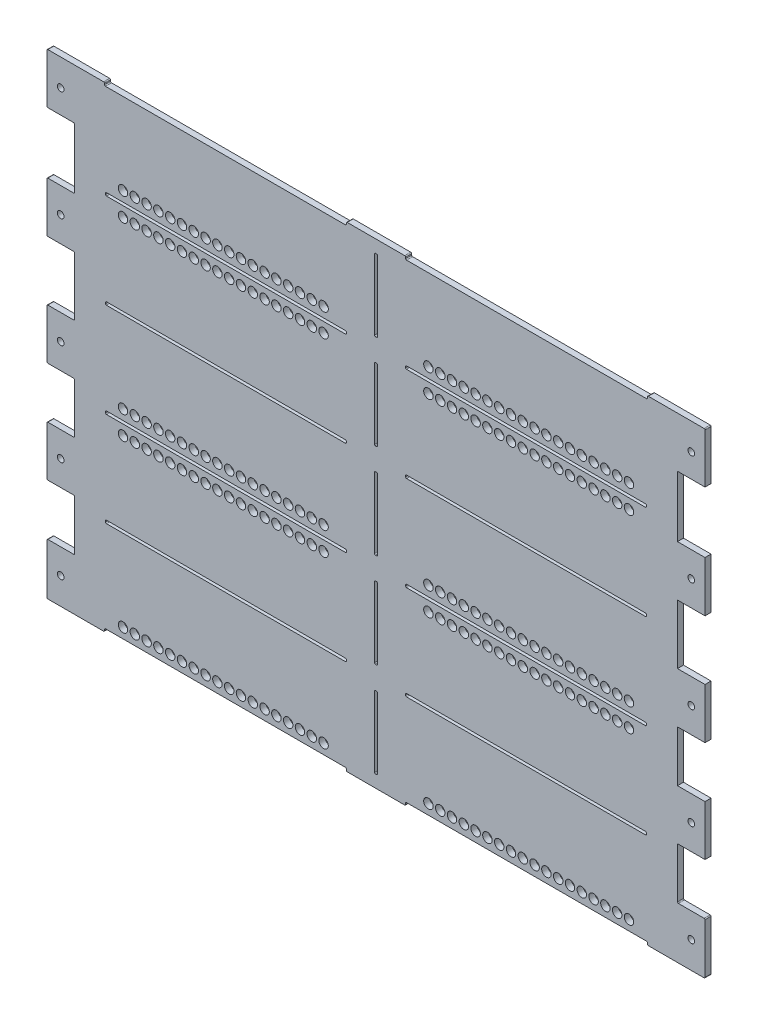
SolidWorks part; units mm, degrees
material "6061-T6 (SS)"
ref_plane "X-Y Datum" through (0, 0, 0) normal (0, 0, 1) x (1, 0, 0)
ref_plane "X-Z Datum" through (0, 0, 0) normal (0, 1, 0) x (1, 0, 0)
ref_plane "Y-Z Datum" through (0, 0, 0) normal (1, 0, 0) x (0, 0, -1)
sketch "Sketch1" plane through (0, 0, 0) normal (0, 0, 1) x (1, 0, 0)
  line L0 (-1.27, -1.27) -> (-1.27, 95.3084)
  line L1 (0, 0) -> (310.8274, 0)
  line L2 (0, 0) -> (0, 94.0384)
  line L3 (0, 94.0384) -> (310.8274, 94.0384)
  line L4 (310.8274, 0) -> (310.8274, 94.0384)
  line L5 (-1.27, 95.3084) -> (312.0974, 95.3084)
  line L6 (312.0974, -1.27) -> (312.0974, 95.3084)
  line L7 (-1.27, -1.27) -> (312.0974, -1.27)
  line L8 (-2.8575, 96.8959) -> (313.6849, 96.8959)
  line L9 (313.6849, -2.8575) -> (313.6849, 96.8959)
  line L10 (-2.8575, -2.8575) -> (313.6849, -2.8575)
  line L11 (-2.8575, -2.8575) -> (-2.8575, 96.8959)
  line L12 (0, 99.7534) -> (310.8274, 99.7534)
  line L13 (310.8274, 193.7918) -> (310.8274, 99.7534)
  line L14 (0, 193.7918) -> (310.8274, 193.7918)
  line L15 (0, 193.7918) -> (0, 99.7534)
  line L16 (-1.27, 195.0618) -> (312.0974, 195.0618)
  line L17 (312.0974, 195.0618) -> (312.0974, 98.4834)
  line L18 (-1.27, 98.4834) -> (312.0974, 98.4834)
  line L19 (-1.27, 195.0618) -> (-1.27, 98.4834)
  line L20 (-2.8575, 196.6493) -> (-2.8575, 96.8959)
  line L21 (-2.8575, 196.6493) -> (630.2273, 196.6493)
  line L23 (-2.8575, 296.4028) -> (630.2273, 296.4028)
  line L24 (-1.27, 198.2368) -> (-1.27, 294.8153)
  line L25 (-1.27, 294.8153) -> (312.0974, 294.8153)
  line L26 (312.0974, 198.2368) -> (312.0974, 294.8153)
  line L27 (-1.27, 198.2368) -> (312.0974, 198.2368)
  line L28 (0, 199.5068) -> (0, 293.5453)
  line L29 (0, 199.5068) -> (310.8274, 199.5068)
  line L30 (310.8274, 199.5068) -> (310.8274, 293.5453)
  line L31 (0, 293.5453) -> (310.8274, 293.5453)
  line L33 (313.6849, 96.8959) -> (313.6849, 196.6493)
  line L34 (-2.8575, 396.1562) -> (630.2273, 396.1562)
  line L35 (-1.27, 394.5687) -> (312.0974, 394.5687)
  line L36 (312.0974, 394.5687) -> (312.0974, 297.9903)
  line L37 (-1.27, 297.9903) -> (312.0974, 297.9903)
  line L38 (-1.27, 394.5687) -> (-1.27, 297.9903)
  line L39 (0, 393.2987) -> (310.8274, 393.2987)
  line L40 (310.8274, 393.2987) -> (310.8274, 299.2603)
  line L41 (0, 299.2603) -> (310.8274, 299.2603)
  line L42 (0, 393.2987) -> (0, 299.2603)
  line L43 (-2.8575, 296.4028) -> (-2.8575, 196.6493)
  line L44 (-2.8575, 495.9096) -> (-2.8575, 296.4028)
  line L45 (313.6849, 495.9096) -> (313.6849, 296.4028)
  line L46 (313.6849, 196.6493) -> (313.6849, 296.4028)
  line L47 (-2.8575, 495.9096) -> (630.2273, 495.9096)
  line L48 (-1.27, 397.7437) -> (-1.27, 494.3221)
  line L49 (-1.27, 494.3221) -> (312.0974, 494.3221)
  line L50 (312.0974, 397.7437) -> (312.0974, 494.3221)
  line L51 (-1.27, 397.7437) -> (312.0974, 397.7437)
  line L52 (0, 399.0137) -> (0, 493.0521)
  line L53 (0, 493.0521) -> (310.8274, 493.0521)
  line L54 (310.8274, 399.0137) -> (310.8274, 493.0521)
  line L55 (0, 399.0137) -> (310.8274, 399.0137)
  line L56 (313.6849, 595.663) -> (313.6849, 495.9096) construction
  line L57 (628.6398, 397.7437) -> (315.2724, 397.7437)
  line L58 (315.2724, 397.7437) -> (315.2724, 494.3221)
  line L59 (628.6398, 494.3221) -> (315.2724, 494.3221)
  line L60 (628.6398, 397.7437) -> (628.6398, 494.3221)
  line L61 (627.3698, 399.0137) -> (316.5424, 399.0137)
  line L62 (316.5424, 399.0137) -> (316.5424, 493.0521)
  line L63 (627.3698, 493.0521) -> (316.5424, 493.0521)
  line L64 (627.3698, 399.0137) -> (627.3698, 493.0521)
  line L65 (630.2273, 495.9096) -> (630.2273, 296.4028)
  line L66 (628.6398, 394.5687) -> (628.6398, 297.9903)
  line L67 (628.6398, 297.9903) -> (315.2724, 297.9903)
  line L68 (315.2724, 394.5687) -> (315.2724, 297.9903)
  line L69 (628.6398, 394.5687) -> (315.2724, 394.5687)
  line L70 (627.3698, 393.2987) -> (627.3698, 299.2603)
  line L71 (627.3698, 299.2603) -> (316.5424, 299.2603)
  line L72 (316.5424, 393.2987) -> (316.5424, 299.2603)
  line L73 (627.3698, 393.2987) -> (316.5424, 393.2987)
  line L74 (630.2273, 296.4028) -> (630.2273, 196.6493)
  line L75 (628.6398, 198.2368) -> (315.2724, 198.2368)
  line L76 (315.2724, 198.2368) -> (315.2724, 294.8153)
  line L77 (628.6398, 294.8153) -> (315.2724, 294.8153)
  line L78 (628.6398, 198.2368) -> (628.6398, 294.8153)
  line L79 (627.3698, 199.5068) -> (316.5424, 199.5068)
  line L80 (316.5424, 199.5068) -> (316.5424, 293.5453)
  line L81 (627.3698, 293.5453) -> (316.5424, 293.5453)
  line L82 (627.3698, 199.5068) -> (627.3698, 293.5453)
  line L83 (630.2273, 196.6493) -> (630.2273, 96.8959)
  line L84 (628.6398, 195.0618) -> (628.6398, 98.4834)
  line L85 (628.6398, 98.4834) -> (315.2724, 98.4834)
  line L86 (315.2724, 195.0618) -> (315.2724, 98.4834)
  line L87 (628.6398, 195.0618) -> (315.2724, 195.0618)
  line L88 (627.3698, 193.7918) -> (627.3698, 99.7534)
  line L89 (627.3698, 193.7918) -> (316.5424, 193.7918)
  line L90 (316.5424, 193.7918) -> (316.5424, 99.7534)
  line L91 (627.3698, 99.7534) -> (316.5424, 99.7534)
  line L92 (630.2273, -2.8575) -> (630.2273, 96.8959)
  line L93 (630.2273, -2.8575) -> (313.6849, -2.8575)
  line L94 (313.6849, -2.8575) -> (313.6849, 96.8959)
  line L95 (630.2273, 96.8959) -> (313.6849, 96.8959)
  line L96 (628.6398, -1.27) -> (315.2724, -1.27)
  line L97 (315.2724, -1.27) -> (315.2724, 95.3084)
  line L98 (628.6398, 95.3084) -> (315.2724, 95.3084)
  line L99 (628.6398, -1.27) -> (628.6398, 95.3084)
  line L100 (627.3698, 94.0384) -> (316.5424, 94.0384)
  line L101 (316.5424, 0) -> (316.5424, 94.0384)
  line L102 (627.3698, 0) -> (316.5424, 0)
  line L103 (627.3698, 0) -> (627.3698, 94.0384)
  point P56 (313.6849, 396.1562)
  dimension "D1" = 310.8274
  dimension "D2" = 94.0384
  dimension "D3" = 1.27
  dimension "D4" = 1.5875
sketch "Sketch2" plane through (0, 0, 0) normal (0, 0, 1) x (1, 0, 0)
  line L0 (0, 47.0192) -> (310.8274, 47.0192) construction
  line L1 (-1.27, -1.27) -> (628.6398, -1.27)
  line L2 (-1.27, -1.27) -> (-1.27, 494.3221)
  line L3 (-1.27, 494.3221) -> (628.6398, 494.3221)
  line L4 (628.6398, -1.27) -> (628.6398, 494.3221)
  line L5 (0, 0) -> (0, 94.0384) construction
  line L6 (310.8274, 0) -> (310.8274, 94.0384) construction
  line L7 (155.4137, 47.0192) -> (155.4137, 163.8162) construction
  line L8 (-2.8575, 96.8959) -> (313.6849, 96.8959) construction
  line L9 (28.4137, 95.3084) -> (282.4137, 95.3084)
  line L10 (28.4137, 95.3084) -> (28.4137, 98.4834)
  line L11 (28.4137, 98.4834) -> (282.4137, 98.4834)
  line L12 (282.4137, 95.3084) -> (282.4137, 98.4834)
  line L13 (28.4137, 95.3084) -> (282.4137, 98.4834) construction
  line L14 (28.4137, 98.4834) -> (282.4137, 95.3084) construction
  line L15 (-1.27, 98.4834) -> (312.0974, 98.4834) construction
  line L16 (-2.8575, 196.6493) -> (630.2273, 196.6493) construction
  line L17 (28.4137, 195.0618) -> (282.4137, 195.0618)
  line L18 (28.4137, 195.0618) -> (28.4137, 198.2368)
  line L19 (28.4137, 198.2368) -> (282.4137, 198.2368)
  line L20 (282.4137, 195.0618) -> (282.4137, 198.2368)
  line L21 (28.4137, 195.0618) -> (282.4137, 198.2368) construction
  line L22 (28.4137, 198.2368) -> (282.4137, 195.0618) construction
  line L23 (-1.27, 198.2368) -> (312.0974, 198.2368) construction
  line L24 (315.2724, -1.27) -> (315.2724, 95.3084) construction
  line L25 (-2.8575, 296.4028) -> (630.2273, 296.4028) construction
  line L26 (28.4137, 294.8153) -> (282.4137, 294.8153)
  line L27 (28.4137, 294.8153) -> (28.4137, 297.9903)
  line L28 (28.4137, 297.9903) -> (282.4137, 297.9903)
  line L29 (282.4137, 294.8153) -> (282.4137, 297.9903)
  line L30 (28.4137, 294.8153) -> (282.4137, 297.9903) construction
  line L31 (28.4137, 297.9903) -> (282.4137, 294.8153) construction
  line L32 (-1.27, 297.9903) -> (312.0974, 297.9903) construction
  line L33 (-2.8575, 396.1562) -> (630.2273, 396.1562) construction
  line L34 (28.4137, 394.5687) -> (282.4137, 394.5687)
  line L35 (28.4137, 394.5687) -> (28.4137, 397.7437)
  line L36 (28.4137, 397.7437) -> (282.4137, 397.7437)
  line L37 (282.4137, 394.5687) -> (282.4137, 397.7437)
  line L38 (28.4137, 394.5687) -> (282.4137, 397.7437) construction
  line L39 (28.4137, 397.7437) -> (282.4137, 394.5687) construction
  line L40 (-1.27, 397.7437) -> (312.0974, 397.7437) construction
  line L41 (313.6849, 604.3732) -> (313.6849, -52.4712) construction
  line L42 (598.9561, 98.4834) -> (344.9561, 98.4834)
  line L43 (344.9561, 95.3084) -> (344.9561, 98.4834)
  line L44 (598.9561, 95.3084) -> (344.9561, 95.3084)
  line L45 (598.9561, 95.3084) -> (598.9561, 98.4834)
  line L46 (598.9561, 198.2368) -> (344.9561, 198.2368)
  line L47 (344.9561, 195.0618) -> (344.9561, 198.2368)
  line L48 (598.9561, 195.0618) -> (344.9561, 195.0618)
  line L49 (598.9561, 195.0618) -> (598.9561, 198.2368)
  line L50 (598.9561, 397.7437) -> (344.9561, 397.7437)
  line L51 (344.9561, 394.5687) -> (344.9561, 397.7437)
  line L52 (598.9561, 394.5687) -> (344.9561, 394.5687)
  line L53 (598.9561, 394.5687) -> (598.9561, 397.7437)
  line L54 (598.9561, 297.9903) -> (344.9561, 297.9903)
  line L55 (344.9561, 294.8153) -> (344.9561, 297.9903)
  line L56 (598.9561, 294.8153) -> (344.9561, 294.8153)
  line L57 (598.9561, 294.8153) -> (598.9561, 297.9903)
  line L58 (312.0974, 8.5255) -> (315.2724, 8.5255)
  line L59 (312.0974, 8.5255) -> (312.0974, 84.7255)
  line L60 (312.0974, 84.7255) -> (315.2724, 84.7255)
  line L61 (315.2724, 8.5255) -> (315.2724, 84.7255)
  line L62 (312.0974, 8.5255) -> (315.2724, 84.7255) construction
  line L63 (312.0974, 84.7255) -> (315.2724, 8.5255) construction
  line L64 (310.8274, 193.7918) -> (310.8274, 99.7534) construction
  line L65 (310.8274, 146.7726) -> (337.6409, 146.7726) construction
  line L66 (315.2724, 195.0618) -> (315.2724, 98.4834) construction
  line L67 (312.0974, 108.6726) -> (315.2724, 108.6726)
  line L68 (312.0974, 108.6726) -> (312.0974, 184.8726)
  line L69 (312.0974, 184.8726) -> (315.2724, 184.8726)
  line L70 (315.2724, 108.6726) -> (315.2724, 184.8726)
  line L71 (312.0974, 108.6726) -> (315.2724, 184.8726) construction
  line L72 (312.0974, 184.8726) -> (315.2724, 108.6726) construction
  line L73 (310.8274, 293.5453) -> (310.8274, 199.5068) construction
  line L74 (310.8274, 246.5261) -> (343.3258, 246.5261) construction
  line L75 (315.2724, 198.2368) -> (315.2724, 294.8153) construction
  line L76 (312.0974, 208.4261) -> (315.2724, 208.4261)
  line L77 (312.0974, 208.4261) -> (312.0974, 284.6261)
  line L78 (312.0974, 284.6261) -> (315.2724, 284.6261)
  line L79 (315.2724, 208.4261) -> (315.2724, 284.6261)
  line L80 (312.0974, 208.4261) -> (315.2724, 284.6261) construction
  line L81 (312.0974, 284.6261) -> (315.2724, 208.4261) construction
  line L82 (310.8274, 299.2603) -> (310.8274, 393.2987) construction
  line L83 (310.8274, 493.0521) -> (310.8274, 399.0137) construction
  line L84 (310.8274, 346.2795) -> (351.536, 346.2795) construction
  line L85 (310.8274, 446.0329) -> (345.4409, 446.0329) construction
  line L86 (315.2724, 394.5687) -> (315.2724, 297.9903) construction
  line L87 (312.0974, 308.1795) -> (315.2724, 308.1795)
  line L88 (312.0974, 308.1795) -> (312.0974, 384.3795)
  line L89 (312.0974, 384.3795) -> (315.2724, 384.3795)
  line L90 (315.2724, 308.1795) -> (315.2724, 384.3795)
  line L91 (312.0974, 308.1795) -> (315.2724, 384.3795) construction
  line L92 (312.0974, 384.3795) -> (315.2724, 308.1795) construction
  line L93 (315.2724, 397.7437) -> (315.2724, 494.3221) construction
  line L94 (312.0974, 407.9329) -> (315.2724, 407.9329)
  line L95 (312.0974, 407.9329) -> (312.0974, 484.1329)
  line L96 (312.0974, 484.1329) -> (315.2724, 484.1329)
  line L97 (315.2724, 407.9329) -> (315.2724, 484.1329)
  line L98 (312.0974, 407.9329) -> (315.2724, 484.1329) construction
  line L99 (312.0974, 484.1329) -> (315.2724, 407.9329) construction
  point P13 (155.4137, 96.8959)
  point P23 (155.4137, 196.6493)
  point P32 (155.4137, 296.4028)
  point P41 (155.4137, 396.1562)
  point P52 (313.6849, 46.6255)
  point P80 (313.6849, 146.7726)
  point P93 (313.6849, 246.526)
  point P114 (313.6849, 346.2795)
  point P122 (313.6849, 446.0329)
  dimension "D1" = 254
  dimension "D2" = 254
  dimension "D3" = 254
  dimension "D4" = 254
  dimension "D5" = 76.2
  dimension "D6" = 76.2
  dimension "D7" = 3.175
  dimension "D8" = 99.7534
  dimension "D9" = 76.2
  dimension "D10" = 99.7534
  dimension "D11" = 99.7534
  dimension "D12" = 99.7534
  dimension "D13" = 76.2
  dimension "D14" = 76.2
extrude "Boss-Extrude1" add sketch "Sketch2" along normal blind 6.35
sketch "Sketch4" plane through (0, 0, 6.35) normal (0, 0, 1) x (1, 0, 0)
  line L0 (313.6849, 484.1329) -> (313.6849, 506.6663) construction
  line L1 (-1.27, -1.27) -> (27.315, -1.27)
  line L2 (-1.27, -1.27) -> (-1.27, -4.445)
  line L3 (-1.27, -4.445) -> (27.315, -4.445)
  line L4 (628.6398, -1.27) -> (628.6398, -4.445)
  line L6 (27.315, -1.27) -> (27.315, -4.445)
  line L8 (282.4137, -1.27) -> (282.4137, -4.445)
  line L9 (600.0548, -1.27) -> (628.6398, -1.27)
  line L11 (344.9561, -1.27) -> (344.9561, -4.445)
  line L13 (600.0548, -1.27) -> (600.0548, -4.445)
  line L14 (600.0548, -4.445) -> (628.6398, -4.445)
  line L15 (282.4137, -1.27) -> (344.9561, -1.27)
  line L16 (282.4137, -4.445) -> (344.9561, -4.445)
  line L17 (-1.27, 246.526) -> (668.9088, 246.526) construction
  line L18 (-1.27, 494.3221) -> (-1.27, -1.27) construction
  line L19 (600.0548, 494.3221) -> (628.6398, 494.3221)
  line L20 (600.0548, 494.3221) -> (600.0548, 497.4971)
  line L21 (600.0548, 497.4971) -> (628.6398, 497.4971)
  line L22 (628.6398, 494.3221) -> (628.6398, 497.4971)
  line L23 (282.4137, 494.3221) -> (344.9561, 494.3221)
  line L24 (344.9561, 494.3221) -> (344.9561, 497.4971)
  line L25 (282.4137, 497.4971) -> (344.9561, 497.4971)
  line L26 (282.4137, 494.3221) -> (282.4137, 497.4971)
  line L27 (-1.27, 494.3221) -> (27.315, 494.3221)
  line L28 (-1.27, 494.3221) -> (-1.27, 497.4971)
  line L29 (-1.27, 497.4971) -> (27.315, 497.4971)
  line L30 (27.315, 494.3221) -> (27.315, 497.4971)
extrude "Boss-Extrude2" add sketch "Sketch4" against normal through all contours L3 L0 L1 L8 L6 L2 | L0 L3 L4 L1 L13 L11 | L13 L14 L4 L9 | L26 L23 L24 L25 | L19 L22 L21 L20 | L8 L16 L11 L15 | L4 L14 L13 L9 | L29 L30 L27 L28 region at (13.0225, -2.8575, 6.35) region at (614.3473, -2.8575, 6.35) region at (614.3473, 495.9096, 6.35) region at (313.6849, 495.9096, 6.35)
sketch "Sketch5" plane through (0, 0, 6.35) normal (0, 0, 1) x (1, 0, 0)
  line L0 (313.6849, 646.2482) -> (313.6849, -137.2183) construction
  line L9 (628.6398, 526.4531) -> (469.3361, 526.4531) construction
  line L18 (469.3361, 510.1236) -> (469.3361, 526.4531) construction
  line L19 (-1.27, 494.3221) -> (628.6398, 494.3221) construction
  line L20 (-1.27, 494.3221) -> (-1.27, 497.4971) construction
  line L21 (158.0337, 510.1236) -> (469.3361, 510.1236) construction
  line L22 (628.6398, 494.3221) -> (628.6398, 497.4971) construction
  line L24 (-1.27, 497.4971) -> (-1.27, 526.4531) construction
  line L25 (-1.27, 526.4531) -> (158.0337, 526.4531) construction
  line L26 (158.0337, 510.1236) -> (158.0337, 526.4531) construction
  line L28 (628.6398, 497.4971) -> (628.6398, 526.4531) construction
  line L29 (-1.27, 244.9386) -> (684.2814, 244.9386) construction
  line L30 (-33.401, 494.3221) -> (-33.401, 497.4971)
  line L41 (628.6398, 494.3221) -> (628.6398, -4.445)
  line L43 (660.7708, 494.3221) -> (660.7708, -4.445)
  line L44 (628.6398, -4.445) -> (660.7708, -4.445)
  line L45 (-1.27, -4.445) -> (-33.401, -4.445)
  line L46 (-33.401, 494.3221) -> (-33.401, -4.445)
  line L48 (-1.27, 494.3221) -> (-1.27, -4.445)
  line L49 (-33.401, 497.4971) -> (-1.27, 497.4971)
  line L50 (-1.27, 497.4971) -> (-1.27, 494.3221)
  line L51 (628.6398, 497.4971) -> (660.7708, 497.4971)
  line L52 (660.7708, 497.4971) -> (660.7708, 494.3221)
  line L53 (628.6398, 497.4971) -> (628.6398, 494.3221)
extrude "Boss-Extrude3" add sketch "Sketch5" against normal through all
sketch "Sketch6" plane through (0, 0, 6.35) normal (0, 0, 1) x (1, 0, 0)
  line L0 (-33.401, 497.4971) -> (-33.401, -4.445) construction
  line L1 (-18.923, 237.4868) -> (-18.923, 23.73) construction
  line L2 (-58.003, 491.1471) -> (-58.003, 0) construction
  line L4 (-33.401, -4.445) -> (27.315, -4.445) construction
  line L5 (-18.923, 486.1471) -> (-18.923, 469.3221) construction
  line L6 (-18.923, 469.3221) -> (-18.923, 237.4868) construction
  line L7 (313.6849, 494.3221) -> (313.6849, 517.9624) construction
  line L8 (-33.401, 497.4971) -> (27.315, 497.4971) construction
  circle A0 centre (-18.923, 23.73) radius 7.1006 construction
  circle A1 centre (-18.923, 469.3221) radius 7.1006 construction
  circle A2 centre (-18.923, 237.4868) radius 7.1006 construction
  circle A3 centre (-18.923, 130.6084) radius 7.1006 construction
  circle A4 centre (-18.923, 353.4045) radius 7.1006 construction
  point P17 (-18.923, 469.3221)
  point P18 (-18.923, 23.73)
  point P21 (-18.923, 237.4868)
  point P22 (-18.923, 130.6084)
  point P25 (-18.923, 353.4045)
  point P26 (646.2928, 23.73)
  point P27 (646.2928, 130.6084)
  point P28 (646.2928, 237.4868)
  point P30 (646.2928, 353.4045)
  point P31 (646.2928, 469.3221)
  dimension "D1" = 14.478
  dimension "D2" = 28.175
  dimension "D3" = 28.175
hole_wizard "M6 Clearance Hole1" positions "Sketch11" profile "Sketch10" hole size "M6" standard "ANSI Metric" end condition through all
sketch "Sketch11" plane through (0, 0, 6.35) normal (0, 0, 1) x (1, 0, 0)
  line L0 (-18.923, 237.4868) -> (-18.923, 23.73) construction
  point P0 (-18.923, 469.3221)
  point P3 (-18.923, 353.4045)
  point P6 (-18.923, 237.4868)
  point P9 (-18.923, 130.6084)
  point P13 (-18.923, 23.73)
  point P16 (646.2928, 23.73)
  point P19 (646.2928, 130.6084)
  point P22 (646.2928, 237.4868)
  point P25 (646.2928, 353.4045)
  point P28 (646.2928, 469.3221)
sketch "Sketch10" plane through (-18.923, 469.3221, 6.35) normal (1, 0, 0) x (0, -1, 0)
  line L0 (0, 0) -> (0, 6.35)
  line L1 (0, 6.35) -> (3.5, 6.35)
  line L2 (3.5, 6.35) -> (3.5, 0)
  line L5 (3.5, 0) -> (0, 0)
  line L11 (0, -6.35) -> (0, 107.95) construction
  dimension "Thru Hole Dia." = 7
  dimension "Thru Hole Depth" = 6.35
sketch "Sketch13" plane through (0, 0, 6.35) normal (0, 0, 1) x (1, 0, 0)
  line L0 (-33.401, 444.3971) -> (-4.352, 444.3971)
  line L1 (-33.401, 444.3971) -> (-33.401, 380.0674)
  line L2 (-33.401, 380.0674) -> (-4.352, 380.0674)
  line L3 (-4.352, 444.3971) -> (-4.352, 380.0674)
  line L4 (-33.401, 326.7415) -> (-4.352, 326.7415)
  line L5 (-33.401, 326.7415) -> (-33.401, 264.0874)
  line L6 (-33.401, 264.0874) -> (-4.352, 264.0874)
  line L7 (-4.352, 326.7415) -> (-4.352, 264.0874)
  line L8 (-33.401, 210.8862) -> (-4.352, 210.8862)
  line L9 (-33.401, 210.8862) -> (-33.401, 157.0858)
  line L10 (-33.401, 157.0858) -> (-4.352, 157.0858)
  line L11 (-4.352, 210.8862) -> (-4.352, 157.0858)
  line L12 (-33.401, 104.1311) -> (-4.352, 104.1311)
  line L13 (-33.401, 104.1311) -> (-33.401, 50.0164)
  line L14 (-33.401, 50.0164) -> (-4.352, 50.0164)
  line L15 (-4.352, 104.1311) -> (-4.352, 50.0164)
  line L32 (-33.494, 492.6971) -> (660.7708, 492.6971) construction
  line L33 (-33.494, 492.6971) -> (-33.494, -1.3734) construction
  line L34 (-33.494, -1.3734) -> (660.7708, -1.3734) construction
  line L36 (313.6849, 84.7255) -> (313.6849, 116.6988) construction
  line L37 (-33.401, 497.4971) -> (-4.445, 497.4971) construction
  line L38 (-33.401, 497.4971) -> (-33.401, 444.3971) construction
  line L39 (-33.401, 444.3971) -> (-4.445, 444.3971) construction
  line L40 (-4.445, 497.4971) -> (-4.445, 444.3971) construction
  line L41 (-4.352, 326.7415) -> (-33.494, 326.7415) construction
  line L42 (-4.352, 326.7415) -> (-4.352, 380.0674) construction
  line L43 (-4.352, 380.0674) -> (-33.494, 380.0674) construction
  line L44 (-33.494, 326.7415) -> (-33.494, 380.0674) construction
  line L45 (-4.352, 326.7415) -> (-33.494, 380.0674) construction
  line L46 (-4.352, 380.0674) -> (-33.494, 326.7415) construction
  line L47 (-33.494, 210.8862) -> (-4.352, 210.8862) construction
  line L48 (-33.494, 210.8862) -> (-33.494, 264.0874) construction
  line L49 (-33.494, 264.0874) -> (-4.352, 264.0874) construction
  line L50 (-4.352, 210.8862) -> (-4.352, 264.0874) construction
  line L51 (-33.494, 210.8862) -> (-4.352, 264.0874) construction
  line L52 (-33.494, 264.0874) -> (-4.352, 210.8862) construction
  line L53 (-33.494, 104.1311) -> (-4.352, 104.1311) construction
  line L54 (-33.494, 104.1311) -> (-33.494, 157.0858) construction
  line L55 (-33.494, 157.0858) -> (-4.352, 157.0858) construction
  line L56 (-4.352, 104.1311) -> (-4.352, 157.0858) construction
  line L57 (-33.494, 104.1311) -> (-4.352, 157.0858) construction
  line L58 (-33.494, 157.0858) -> (-4.352, 104.1311) construction
  line L59 (-33.494, -2.5564) -> (-4.352, -2.5564) construction
  line L60 (-33.494, -2.5564) -> (-33.494, 50.0164) construction
  line L61 (-33.494, 50.0164) -> (-4.352, 50.0164) construction
  line L62 (-4.352, -2.5564) -> (-4.352, 50.0164) construction
  line L63 (-33.494, -2.5564) -> (-4.352, 50.0164) construction
  line L64 (-33.494, 50.0164) -> (-4.352, -2.5564) construction
  line L66 (660.7708, 104.1311) -> (660.7708, 50.0164)
  line L67 (660.7708, 50.0164) -> (631.7219, 50.0164)
  line L68 (631.7219, 104.1311) -> (631.7219, 50.0164)
  line L69 (660.7708, 104.1311) -> (631.7219, 104.1311)
  line L70 (660.7708, 210.8862) -> (660.7708, 157.0858)
  line L71 (660.7708, 157.0858) -> (631.7219, 157.0858)
  line L72 (631.7219, 210.8862) -> (631.7219, 157.0858)
  line L73 (660.7708, 210.8862) -> (631.7219, 210.8862)
  line L74 (660.7708, 326.7415) -> (660.7708, 264.0874)
  line L75 (660.7708, 264.0874) -> (631.7219, 264.0874)
  line L76 (631.7219, 326.7415) -> (631.7219, 264.0874)
  line L77 (660.7708, 326.7415) -> (631.7219, 326.7415)
  line L78 (660.7708, 444.3971) -> (660.7708, 380.0674)
  line L79 (660.7708, 380.0674) -> (631.7219, 380.0674)
  line L80 (631.7219, 444.3971) -> (631.7219, 380.0674)
  line L81 (660.7708, 444.3971) -> (631.7219, 444.3971)
  point P1 (-18.923, 237.4868)
  point P5 (-18.923, 130.6084)
  point P9 (-18.923, 23.73)
  point P41 (-18.923, 353.4045)
extrude "Cut-Extrude1" cut sketch "Sketch13" against normal through all
sketch "Sketch15" plane through (0, 0, 0) normal (0, 0, 1) x (1, 0, 0)
  line L0 (28.4137, 397.7437) -> (282.4137, 397.7437) construction
  line L1 (28.4137, 394.5687) -> (279.5273, 394.5687) construction
  line L2 (28.4137, 394.5687) -> (282.4137, 394.5687) construction
  line L7 (-1.27, 491.1471) -> (628.6398, 491.1471) construction
  line L8 (-1.27, 491.1471) -> (-1.27, 0.1766) construction
  line L9 (-1.27, 0.1766) -> (628.6398, 0.1766) construction
  line L10 (628.6398, 491.1471) -> (628.6398, 0.1766) construction
  line L11 (28.4137, 198.2368) -> (282.4137, 198.2368) construction
  line L12 (282.4137, 195.0618) -> (28.4137, 195.0618) construction
  line L13 (27.315, -1.27) -> (282.4137, -1.27) construction
  line L14 (313.6849, 484.1329) -> (313.6849, 511.0054) construction
  circle A0 centre (46.8046, 408.4117) radius 5
  circle A19 centre (46.8046, 383.9007) radius 5
  circle A38 centre (46.8046, 208.9048) radius 5
  circle A39 centre (46.8046, 184.3938) radius 5
  circle A40 centre (46.8046, 9.398) radius 5
  circle A41 centre (59.2506, 408.4117) radius 5
  circle A42 centre (59.2506, 383.9007) radius 5
  circle A43 centre (59.2506, 208.9048) radius 5
  circle A44 centre (59.2506, 184.3938) radius 5
  circle A45 centre (59.2506, 9.398) radius 5
  circle A46 centre (71.6966, 408.4117) radius 5
  circle A47 centre (71.6966, 383.9007) radius 5
  circle A48 centre (71.6966, 208.9048) radius 5
  circle A49 centre (71.6966, 184.3938) radius 5
  circle A50 centre (71.6966, 9.398) radius 5
  circle A51 centre (84.1426, 408.4117) radius 5
  circle A52 centre (84.1426, 383.9007) radius 5
  circle A53 centre (84.1426, 208.9048) radius 5
  circle A54 centre (84.1426, 184.3938) radius 5
  circle A55 centre (84.1426, 9.398) radius 5
  circle A56 centre (96.5886, 408.4117) radius 5
  circle A57 centre (96.5886, 383.9007) radius 5
  circle A58 centre (96.5886, 208.9048) radius 5
  circle A59 centre (96.5886, 184.3938) radius 5
  circle A60 centre (96.5886, 9.398) radius 5
  circle A61 centre (109.0346, 408.4117) radius 5
  circle A62 centre (109.0346, 383.9007) radius 5
  circle A63 centre (109.0346, 208.9048) radius 5
  circle A64 centre (109.0346, 184.3938) radius 5
  circle A65 centre (109.0346, 9.398) radius 5
  circle A66 centre (121.4806, 408.4117) radius 5
  circle A67 centre (121.4806, 383.9007) radius 5
  circle A68 centre (121.4806, 208.9048) radius 5
  circle A69 centre (121.4806, 184.3938) radius 5
  circle A70 centre (121.4806, 9.398) radius 5
  circle A71 centre (133.9266, 408.4117) radius 5
  circle A72 centre (133.9266, 383.9007) radius 5
  circle A73 centre (133.9266, 208.9048) radius 5
  circle A74 centre (133.9266, 184.3938) radius 5
  circle A75 centre (133.9266, 9.398) radius 5
  circle A76 centre (146.3726, 408.4117) radius 5
  circle A77 centre (146.3726, 383.9007) radius 5
  circle A78 centre (146.3726, 208.9048) radius 5
  circle A79 centre (146.3726, 184.3938) radius 5
  circle A80 centre (146.3726, 9.398) radius 5
  circle A81 centre (158.8186, 408.4117) radius 5
  circle A82 centre (158.8186, 383.9007) radius 5
  circle A83 centre (158.8186, 208.9048) radius 5
  circle A84 centre (158.8186, 184.3938) radius 5
  circle A85 centre (158.8186, 9.398) radius 5
  circle A86 centre (171.2646, 408.4117) radius 5
  circle A87 centre (171.2646, 383.9007) radius 5
  circle A88 centre (171.2646, 208.9048) radius 5
  circle A89 centre (171.2646, 184.3938) radius 5
  circle A90 centre (171.2646, 9.398) radius 5
  circle A91 centre (183.7106, 408.4117) radius 5
  circle A92 centre (183.7106, 383.9007) radius 5
  circle A93 centre (183.7106, 208.9048) radius 5
  circle A94 centre (183.7106, 184.3938) radius 5
  circle A95 centre (183.7106, 9.398) radius 5
  circle A96 centre (196.1566, 408.4117) radius 5
  circle A97 centre (196.1566, 383.9007) radius 5
  circle A98 centre (196.1566, 208.9048) radius 5
  circle A99 centre (196.1566, 184.3938) radius 5
  circle A100 centre (196.1566, 9.398) radius 5
  circle A101 centre (208.6026, 408.4117) radius 5
  circle A102 centre (208.6026, 383.9007) radius 5
  circle A103 centre (208.6026, 208.9048) radius 5
  circle A104 centre (208.6026, 184.3938) radius 5
  circle A105 centre (208.6026, 9.398) radius 5
  circle A106 centre (221.0486, 408.4117) radius 5
  circle A107 centre (221.0486, 383.9007) radius 5
  circle A108 centre (221.0486, 208.9048) radius 5
  circle A109 centre (221.0486, 184.3938) radius 5
  circle A110 centre (221.0486, 9.398) radius 5
  circle A111 centre (233.4946, 408.4117) radius 5
  circle A112 centre (233.4946, 383.9007) radius 5
  circle A113 centre (233.4946, 208.9048) radius 5
  circle A114 centre (233.4946, 184.3938) radius 5
  circle A115 centre (233.4946, 9.398) radius 5
  circle A116 centre (245.9406, 408.4117) radius 5
  circle A117 centre (245.9406, 383.9007) radius 5
  circle A118 centre (245.9406, 208.9048) radius 5
  circle A119 centre (245.9406, 184.3938) radius 5
  circle A120 centre (245.9406, 9.398) radius 5
  circle A121 centre (258.3866, 408.4117) radius 5
  circle A122 centre (258.3866, 383.9007) radius 5
  circle A123 centre (258.3866, 208.9048) radius 5
  circle A124 centre (258.3866, 184.3938) radius 5
  circle A125 centre (258.3866, 9.398) radius 5
  circle A216 centre (368.9833, 9.398) radius 5
  circle A217 centre (368.9833, 184.3938) radius 5
  circle A218 centre (368.9833, 208.9048) radius 5
  circle A219 centre (368.9833, 383.9007) radius 5
  circle A220 centre (368.9833, 408.4117) radius 5
  circle A221 centre (381.4293, 9.398) radius 5
  circle A222 centre (381.4293, 184.3938) radius 5
  circle A223 centre (381.4293, 208.9048) radius 5
  circle A224 centre (381.4293, 383.9007) radius 5
  circle A225 centre (381.4293, 408.4117) radius 5
  circle A226 centre (393.8753, 9.398) radius 5
  circle A227 centre (393.8753, 184.3938) radius 5
  circle A228 centre (393.8753, 208.9048) radius 5
  circle A229 centre (393.8753, 383.9007) radius 5
  circle A230 centre (393.8753, 408.4117) radius 5
  circle A231 centre (406.3213, 9.398) radius 5
  circle A232 centre (406.3213, 184.3938) radius 5
  circle A233 centre (406.3213, 208.9048) radius 5
  circle A234 centre (406.3213, 383.9007) radius 5
  circle A235 centre (406.3213, 408.4117) radius 5
  circle A236 centre (418.7673, 9.398) radius 5
  circle A237 centre (418.7673, 184.3938) radius 5
  circle A238 centre (418.7673, 208.9048) radius 5
  circle A239 centre (418.7673, 383.9007) radius 5
  circle A240 centre (418.7673, 408.4117) radius 5
  circle A241 centre (431.2133, 9.398) radius 5
  circle A242 centre (431.2133, 184.3938) radius 5
  circle A243 centre (431.2133, 208.9048) radius 5
  circle A244 centre (431.2133, 383.9007) radius 5
  circle A245 centre (431.2133, 408.4117) radius 5
  circle A246 centre (443.6593, 9.398) radius 5
  circle A247 centre (443.6593, 184.3938) radius 5
  circle A248 centre (443.6593, 208.9048) radius 5
  circle A249 centre (443.6593, 383.9007) radius 5
  circle A250 centre (443.6593, 408.4117) radius 5
  circle A251 centre (456.1053, 9.398) radius 5
  circle A252 centre (456.1053, 184.3938) radius 5
  circle A253 centre (456.1053, 208.9048) radius 5
  circle A254 centre (456.1053, 383.9007) radius 5
  circle A255 centre (456.1053, 408.4117) radius 5
  circle A256 centre (468.5513, 9.398) radius 5
  circle A257 centre (468.5513, 184.3938) radius 5
  circle A258 centre (468.5513, 208.9048) radius 5
  circle A259 centre (468.5513, 383.9007) radius 5
  circle A260 centre (468.5513, 408.4117) radius 5
  circle A261 centre (480.9973, 9.398) radius 5
  circle A262 centre (480.9973, 184.3938) radius 5
  circle A263 centre (480.9973, 208.9048) radius 5
  circle A264 centre (480.9973, 383.9007) radius 5
  circle A265 centre (480.9973, 408.4117) radius 5
  circle A266 centre (493.4433, 9.398) radius 5
  circle A267 centre (493.4433, 184.3938) radius 5
  circle A268 centre (493.4433, 208.9048) radius 5
  circle A269 centre (493.4433, 383.9007) radius 5
  circle A270 centre (493.4433, 408.4117) radius 5
  circle A271 centre (505.8893, 9.398) radius 5
  circle A272 centre (505.8893, 184.3938) radius 5
  circle A273 centre (505.8893, 208.9048) radius 5
  circle A274 centre (505.8893, 383.9007) radius 5
  circle A275 centre (505.8893, 408.4117) radius 5
  circle A276 centre (518.3353, 9.398) radius 5
  circle A277 centre (518.3353, 184.3938) radius 5
  circle A278 centre (518.3353, 208.9048) radius 5
  circle A279 centre (518.3353, 383.9007) radius 5
  circle A280 centre (518.3353, 408.4117) radius 5
  circle A281 centre (530.7813, 9.398) radius 5
  circle A282 centre (530.7813, 184.3938) radius 5
  circle A283 centre (530.7813, 208.9048) radius 5
  circle A284 centre (530.7813, 383.9007) radius 5
  circle A285 centre (530.7813, 408.4117) radius 5
  circle A286 centre (543.2273, 9.398) radius 5
  circle A287 centre (543.2273, 184.3938) radius 5
  circle A288 centre (543.2273, 208.9048) radius 5
  circle A289 centre (543.2273, 383.9007) radius 5
  circle A290 centre (543.2273, 408.4117) radius 5
  circle A291 centre (555.6733, 9.398) radius 5
  circle A292 centre (555.6733, 184.3938) radius 5
  circle A293 centre (555.6733, 208.9048) radius 5
  circle A294 centre (555.6733, 383.9007) radius 5
  circle A295 centre (555.6733, 408.4117) radius 5
  circle A296 centre (568.1193, 9.398) radius 5
  circle A297 centre (568.1193, 184.3938) radius 5
  circle A298 centre (568.1193, 208.9048) radius 5
  circle A299 centre (568.1193, 383.9007) radius 5
  circle A300 centre (568.1193, 408.4117) radius 5
  circle A301 centre (580.5653, 9.398) radius 5
  circle A302 centre (580.5653, 184.3938) radius 5
  circle A303 centre (580.5653, 208.9048) radius 5
  circle A304 centre (580.5653, 383.9007) radius 5
  circle A305 centre (580.5653, 408.4117) radius 5
  dimension "D1" = 18
  dimension "D2" = 10.668
  dimension "D3" = 10.668
  dimension "D4" = 10.668
  dimension "D5" = 10.668
  dimension "D6" = 10.668
extrude "Cut-Extrude5" cut sketch "Sketch15" along normal through all
fillet "Fillet1" radius 1 38 edges at (27.315, 497.4971, 3.175) (27.315, 494.3221, 3.175) (282.4137, 494.3221, 3.175) (282.4137, 497.4971, 3.175) (344.9561, 497.4971, 3.175) (344.9561, 494.3221, 3.175) (600.0548, 494.3221, 3.175) (600.0548, 497.4971, 3.175) (660.7708, 497.4971, 3.175) (660.7708, -4.445, 3.175) (600.0548, -4.445, 3.175) (600.0548, -1.27, 3.175) (344.9561, -1.27, 3.175) (344.9561, -4.445, 3.175) (282.4137, -4.445, 3.175) (282.4137, -1.27, 3.175) (27.315, -1.27, 3.175) (27.315, -4.445, 3.175) (-33.401, -4.445, 3.175) (-33.401, 50.0164, 3.175) (-4.352, 50.0164, 3.175) (-4.352, 104.1311, 3.175) (-33.401, 104.1311, 3.175) (-33.401, 157.0858, 3.175) (-4.352, 157.0858, 3.175) (-4.352, 210.8862, 3.175) (-33.401, 210.8862, 3.175) (-33.401, 264.0874, 3.175) (-4.352, 264.0874, 3.175) (-4.352, 326.7415, 3.175) (-33.401, 326.7415, 3.175) (-33.401, 380.0674, 3.175) (-4.352, 380.0674, 3.175) (-33.401, 444.3971, 3.175) (-4.352, 444.3971, 3.175) (-33.401, 497.4971, 3.175) (631.7219, 50.0164, 3.175) (660.7708, 50.0164, 3.175)
fillet "Fillet2" radius 1 52 edges at (312.0974, 407.9329, 3.175) (315.2724, 407.9329, 3.175) (315.2724, 484.1329, 3.175) (312.0974, 484.1329, 3.175) (312.0974, 384.3795, 3.175) (315.2724, 384.3795, 3.175) (312.0974, 308.1795, 3.175) (315.2724, 308.1795, 3.175) (282.4137, 294.8153, 3.175) (282.4137, 297.9903, 3.175) (28.4137, 297.9903, 3.175) (28.4137, 294.8153, 3.175) (28.4137, 394.5687, 3.175) (28.4137, 397.7437, 3.175) (282.4137, 397.7437, 3.175) (282.4137, 394.5687, 3.175) (344.9561, 394.5687, 3.175) (344.9561, 397.7437, 3.175) (598.9561, 394.5687, 3.175) (598.9561, 397.7437, 3.175) (598.9561, 294.8153, 3.175) (598.9561, 297.9903, 3.175) (344.9561, 297.9903, 3.175) (344.9561, 294.8153, 3.175) (315.2724, 208.4261, 3.175) (312.0974, 208.4261, 3.175) (312.0974, 284.6261, 3.175) (315.2724, 284.6261, 3.175) (282.4137, 195.0618, 3.175) (282.4137, 198.2368, 3.175) (28.4137, 198.2368, 3.175) (28.4137, 195.0618, 3.175) (315.2724, 108.6726, 3.175) (312.0974, 108.6726, 3.175) (315.2724, 184.8726, 3.175) (312.0974, 184.8726, 3.175) (344.9561, 195.0618, 3.175) (344.9561, 198.2368, 3.175) (598.9561, 195.0618, 3.175) (598.9561, 198.2368, 3.175) (598.9561, 95.3084, 3.175) (598.9561, 98.4834, 3.175) (344.9561, 95.3084, 3.175) (344.9561, 98.4834, 3.175) (315.2724, 8.5255, 3.175) (312.0974, 8.5255, 3.175) (312.0974, 84.7255, 3.175) (315.2724, 84.7255, 3.175) (282.4137, 95.3084, 3.175) (282.4137, 98.4834, 3.175) (28.4137, 98.4834, 3.175) (28.4137, 95.3084, 3.175)
